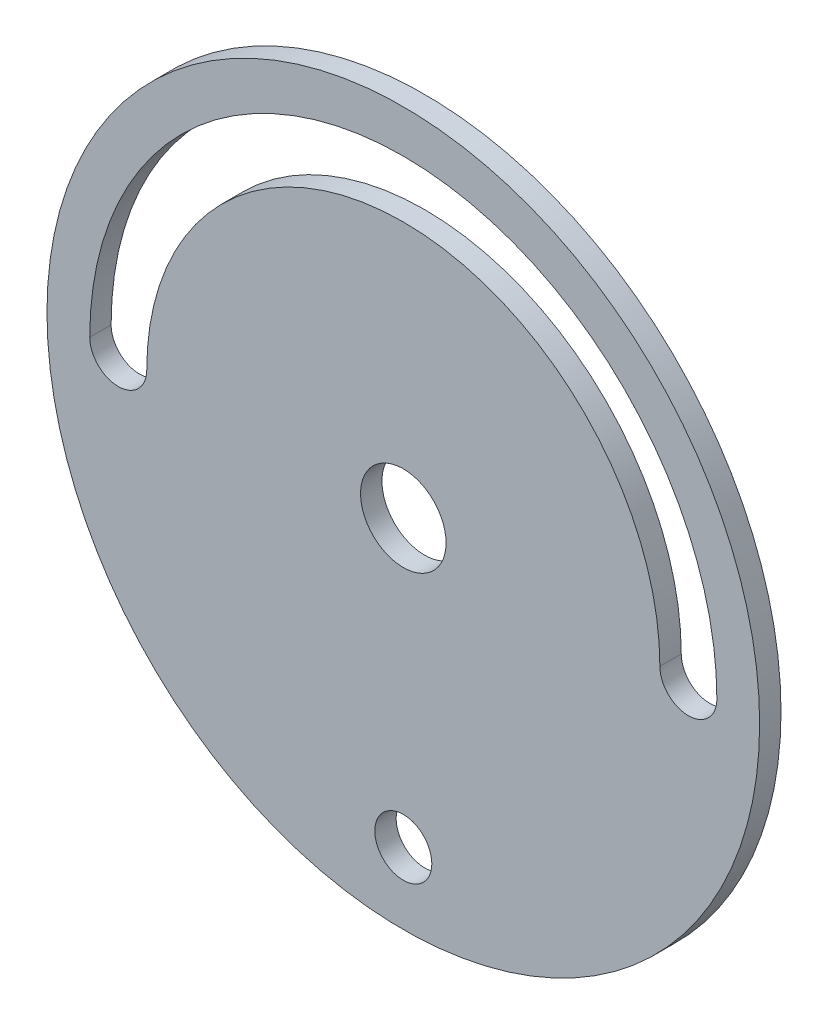
SolidWorks part; units mm, degrees
ref_plane "Front Plane" through (0, 0, 0) normal (0, 0, 1) x (1, 0, 0)
ref_plane "Top Plane" through (0, 0, 0) normal (0, 1, 0) x (1, 0, 0)
ref_plane "Right Plane" through (0, 0, 0) normal (1, 0, 0) x (0, 0, -1)
sketch "Sketch1" plane through (0, 0, 0) normal (0, 0, 1) x (1, 0, 0)
  line L0 (-27.0565, 7.3948) -> (22.9435, 7.3948) construction
  circle A0 centre (-2.0565, 7.3948) radius 25
  circle A2 centre (-2.0565, -12.6052) radius 2
  arc A3 (19.9435, 7.3948) -> (-24.0565, 7.3948) centre (-2.0565, 7.3948) ccw
  arc A4 (15.9435, 7.3948) -> (-20.0565, 7.3948) centre (-2.0565, 7.3948) ccw
  arc A5 (19.9435, 7.3948) -> (15.9435, 7.3948) centre (17.9435, 7.3948) cw
  arc A6 (-24.0565, 7.3948) -> (-20.0565, 7.3948) centre (-22.0565, 7.3948) ccw
  circle A7 centre (-2.0565, 7.3948) radius 3
  dimension "D1" = 4
  dimension "D2" = 50
  dimension "D4" = 6
  dimension "D3" = 20
extrude "Boss-Extrude1" add sketch "Sketch1" along normal blind 1.5
